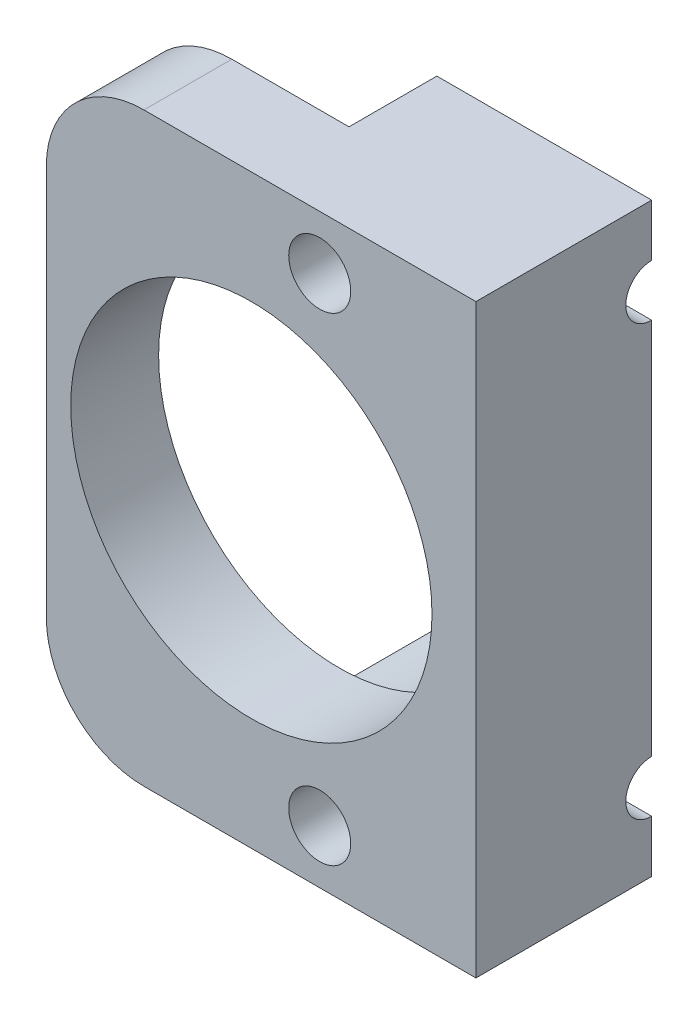
SolidWorks part; units mm, degrees
material "6061-T6 (SS)"
ref_plane "Front Plane" through (0, 0, 0) normal (0, 0, 1) x (1, 0, 0)
ref_plane "Top Plane" through (0, 0, 0) normal (0, 1, 0) x (1, 0, 0)
ref_plane "Right Plane" through (0, 0, 0) normal (1, 0, 0) x (0, 0, -1)
sketch "Sketch1" plane through (0, 0, 0) normal (0, 0, 1) x (1, 0, 0)
  line L0 (-21, 30) -> (-21, -30)
  line L1 (-21, -30) -> (23, -30)
  line L2 (0, 0) -> (18.5, 0) construction
  line L4 (23, 30) -> (23, -30)
  line L5 (-21, 30) -> (23, 30)
  circle A0 centre (0, 0) radius 18.5
  arc A1 (0, 21) -> (-21, 0) centre (0, 0) ccw construction
  arc A2 (-21, 0) -> (0, 21) centre (0, 0) ccw construction
  point P10 (23, 0)
  dimension "D1" = 37
  dimension "D2" = 42
  dimension "D3" = 30
  dimension "D4" = 23
extrude "Boss-Extrude1" add sketch "Sketch1" along normal mid plane 9
sketch "Sketch3" plane through (0, 0, -4.5) normal (0, 0, -1) x (-1, 0, 0)
  line L0 (-23, 30) -> (-1, 30)
  line L1 (-23, 30) -> (21, 30) construction
  line L2 (-1, 30) -> (-1, 18.9737)
  line L3 (-23, 30) -> (-23, -30)
  line L4 (-23, -30) -> (-23, 30) construction
  line L5 (0, 0) -> (-18.5, 0) construction
  line L6 (-23, -30) -> (-1, -30)
  line L7 (-1, -30) -> (-1, -18.9737)
  circle A0 centre (0, 0) radius 18.5 construction
  arc A2 (-1, -18.9737) -> (-1, 18.9737) centre (0, 0) ccw construction
  arc A3 (-1, 18.9737) -> (-1, -18.9737) centre (0, 0) ccw
  dimension "D2" = 19
  dimension "D1" = 1
extrude "Boss-Extrude2" add sketch "Sketch3" along normal blind 9
fillet "Fillet1" radius 10 2 edges at (-21, -30, 0) (-21, 30, 0)
sketch "Sketch5" plane through (0, 0, -13.5) normal (0, 0, -1) x (-1, 0, 0)
  line L1 (-1, 30) -> (-23, 30) construction
  line L3 (0, 0) -> (-18.5, 0) construction
  line L4 (-23, 30) -> (-23, -30) construction
  circle A0 centre (-7, 24.5) radius 3.175
  circle A1 centre (0, 0) radius 18.5 construction
  circle A2 centre (-7, -24.5) radius 3.175
  dimension "D1" = 6.35
  dimension "D2" = 16
  dimension "D3" = 5.5
extrude "Cut-Extrude1" cut sketch "Sketch5" against normal through all
sketch "Sketch6" plane through (0, 0, -13.5) normal (0, 0, -1) x (-1, 0, 0)
  line L0 (-1, 30) -> (-23, 30) construction
  line L1 (-14.5, 22) -> (-14.5, 26) construction
  line L2 (-14.5, 22) -> (-12, 22) construction
  line L3 (-15.5, 18) -> (-13.5, 18)
  line L4 (-17, 19.5) -> (-17, 24.5)
  line L5 (-15.5, 26) -> (-13.5, 26)
  line L6 (-12, 19.5) -> (-12, 24.5)
  line L7 (-17, 18) -> (-12, 26) construction
  line L8 (-17, 26) -> (-12, 18) construction
  line L9 (-23, 30) -> (-23, -30) construction
  line L10 (0, 0) -> (-18.5, 0) construction
  line L15 (-17, 24.5) -> (-17, 26) construction
  line L16 (-17, 26) -> (-15.5, 26) construction
  line L17 (-13.5, 26) -> (-12, 26) construction
  line L18 (-12, 24.5) -> (-12, 26) construction
  line L19 (-12, 18) -> (-12, 19.5) construction
  line L20 (-13.5, 18) -> (-12, 18) construction
  line L21 (-17, 18) -> (-15.5, 18) construction
  line L22 (-17, 18) -> (-17, 19.5) construction
  line L23 (-15.5, -18) -> (-13.5, -18)
  line L24 (-12, -19.5) -> (-12, -24.5)
  line L25 (-15.5, -26) -> (-13.5, -26)
  line L26 (-17, -19.5) -> (-17, -24.5)
  circle A2 centre (0, 0) radius 18.5 construction
  arc A4 (-17, 24.5) -> (-15.5, 26) centre (-16.25, 25.25) cw
  arc A5 (-12, 24.5) -> (-13.5, 26) centre (-12.75, 25.25) ccw
  arc A6 (-12, 19.5) -> (-13.5, 18) centre (-12.75, 18.75) cw
  arc A7 (-17, 19.5) -> (-15.5, 18) centre (-16.25, 18.75) ccw
  arc A8 (-17, -19.5) -> (-15.5, -18) centre (-16.25, -18.75) cw
  arc A9 (-12, -19.5) -> (-13.5, -18) centre (-12.75, -18.75) ccw
  arc A10 (-12, -24.5) -> (-13.5, -26) centre (-12.75, -25.25) cw
  arc A11 (-17, -24.5) -> (-15.5, -26) centre (-16.25, -25.25) ccw
  point P0 (-14.5, 22)
  point P42 (-12, 22)
  point P43 (-14.5, 26)
  dimension "D3" = 4
  dimension "D5" = 1.5
  dimension "D1" = 8
  dimension "D2" = 5
  dimension "D4" = 6
  dimension "D6" = 1.5
extrude "Cut-Extrude2" cut sketch "Sketch6" against normal blind 4.75
fillet "Fillet2" radius 1 16 edges at (17, -19.5, -11.125) (17, -24.5, -11.125) (15.5, -26, -11.125) (13.5, -26, -11.125) (12, -24.5, -11.125) (12, -19.5, -11.125) (13.5, -18, -11.125) (15.5, -18, -11.125) (17, 24.5, -11.125) (17, 19.5, -11.125) (15.5, 18, -11.125) (13.5, 18, -11.125) (12, 19.5, -11.125) (12, 24.5, -11.125) (13.5, 26, -11.125) (15.5, 26, -11.125)
sketch "Sketch8" plane through (17, 0, 0) normal (-1, 0, 0) x (0, 0, 1)
  line L0 (-13.5, -19.838) -> (-13.5, -24.162) construction
  line L1 (-13.5, 24.162) -> (-13.5, 19.838) construction
  point P0 (-13.5, 22)
  point P1 (-13.5, -22)
hole_wizard "M5 Clearance Hole1" positions "Sketch9" profile "Sketch10" hole size "M5" standard "ANSI Metric" end condition through all
sketch "Sketch9" plane through (17, 0, 0) normal (-1, 0, 0) x (0, 0, 1)
  point P0 (-13.5, -22)
  point P3 (-13.5, 22)
sketch "Sketch10" plane through (17, -22, -13.5) normal (0, 1, 0) x (0, 0, 1)
  line L0 (0, 0) -> (0, 6)
  line L1 (0, 6) -> (2.65, 6)
  line L2 (2.65, 6) -> (2.65, 0)
  line L5 (2.65, 0) -> (0, 0)
  line L11 (0, -6.35) -> (0, 107.95) construction
  dimension "Thru Hole Dia." = 5.3
  dimension "Thru Hole Depth" = 6
equation "\"D1@Sketch5\"=0.25in"
